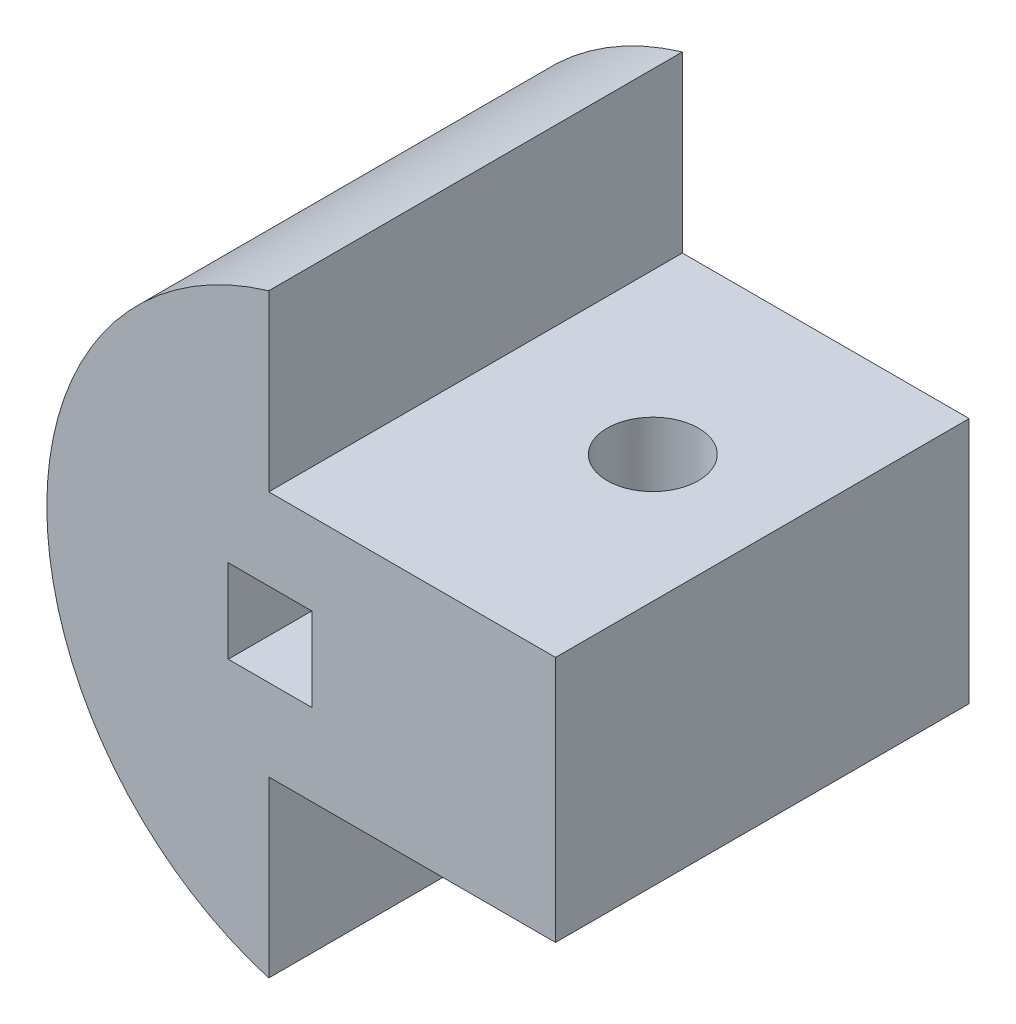
SolidWorks part; units mm, degrees
material "ABS"
ref_plane "Front Plane" through (0, 0, 0) normal (0, 0, 1) x (1, 0, 0)
ref_plane "Top Plane" through (0, 0, 0) normal (0, 1, 0) x (1, 0, 0)
ref_plane "Right Plane" through (0, 0, 0) normal (1, 0, 0) x (0, 0, -1)
sketch "Sketch2" plane through (0, 0, 0) normal (0, 0, 1) x (1, 0, 0)
  line L3 (0, 3) -> (11.5, 3) construction
  line L4 (0, -4) -> (0, 3) construction
  line L5 (11.5, 3) -> (11.5, 8) construction
  line L6 (0, 20) -> (0, 13) construction
  line L7 (0, 13) -> (11.5, 13) construction
  line L8 (11.5, 13) -> (11.5, 8) construction
  line L9 (0, 3) -> (11.5, 3) construction
  line L10 (0, -4) -> (0, 3) construction
  line L11 (11.5, 3) -> (11.5, 8) construction
  line L12 (-0.05, 19.9331) -> (-0.05, 12.95)
  line L13 (-1.675, 9.675) -> (1.675, 9.675)
  line L14 (-1.675, 9.675) -> (-1.675, 6.325)
  line L15 (-1.675, 6.325) -> (1.675, 6.325)
  line L16 (1.675, 9.675) -> (1.675, 6.325)
  line L17 (-1.675, 9.675) -> (1.675, 6.325) construction
  line L18 (-1.675, 6.325) -> (1.675, 9.675) construction
  line L19 (-0.05, 12.95) -> (11.45, 12.95)
  line L20 (11.45, 12.95) -> (11.45, 8)
  line L21 (11.45, 3.05) -> (11.45, 8)
  line L22 (-0.05, 3.05) -> (11.45, 3.05)
  line L23 (-0.05, -3.9331) -> (-0.05, 3.05)
  line L24 (0, 3) -> (0, 13) construction
  line L25 (0, 13) -> (0.029, 13.0264) construction
  arc A0 (0, 20) -> (0, -4) centre (3.5, 8) ccw construction
  arc A1 (-0.05, 19.9331) -> (-0.05, -3.9331) centre (3.5, 8) ccw
  arc A2 (0, 20) -> (0, -4) centre (3.5, 8) ccw construction
  point P7 (0, 8)
  dimension "D1" = 3.35
  dimension "D3" = 8
  dimension "D2" = 0.05
extrude "Boss-Extrude1" add sketch "Sketch2" against normal up to surface (16.586 mm away) contours L12 A1 L23 L22 L21 L20 L19 L13 L16 L15 L14 region at (-0.364, 16.4416, 0)
sketch "Sketch3" plane through (0, 0, 0) normal (0, 0, 1) x (1, 0, 0)
  line L0 (-1.675, 8) -> (1.675, 8)
  line L1 (-1.675, 9.675) -> (-1.675, 6.325) construction
  line L2 (1.675, 9.675) -> (1.675, 6.325) construction
  point P0 (0, 8)
ref_axis "Axis1" through (0, 8, 0) along (0, 0, 1)
sketch "Sketch4" plane through (0, 3.05, 0) normal (0, -1, 0) x (1, 0, 0)
  circle A0 centre (6.35, -9) radius 1.8288 construction
  circle A1 centre (6.35, -9) radius 1.8288
extrude "Cut-Extrude1" cut sketch "Sketch4" against normal through all
